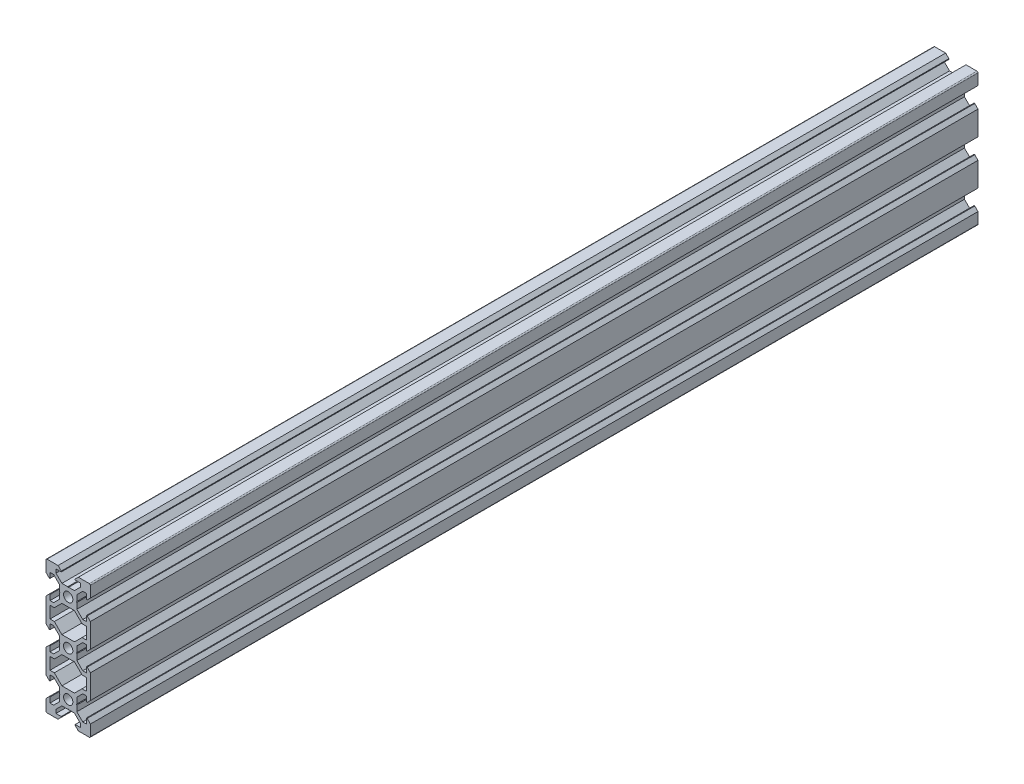
SolidWorks part; units mm, degrees
material "6061-T6 (SS)"
ref_plane "Front Plane" through (0, 0, 0) normal (0, 0, 1) x (1, 0, 0)
ref_plane "Top Plane" through (0, 0, 0) normal (0, 1, 0) x (1, 0, 0)
ref_plane "Right Plane" through (0, 0, 0) normal (1, 0, 0) x (0, 0, -1)
sketch "Sketch1" plane through (0, 0, 0) normal (0, 0, 1) x (1, 0, 0)
  line L0 (0, 0) -> (10, 0) construction
  line L1 (9.5, -30) -> (-9.5, -30)
  line L2 (10, -29.5) -> (10, 29.5)
  line L3 (9.5, 30) -> (-9.5, 30)
  line L4 (-10, -29.5) -> (-10, 29.5)
  line L5 (10, -30) -> (-10, 30) construction
  line L6 (10, 30) -> (-10, -30) construction
  circle A0 centre (0, 20) radius 2.1
  circle A1 centre (0, 0) radius 2.1
  circle A2 centre (0, -20) radius 2.1
  arc A3 (-9.5, -30) -> (-10, -29.5) centre (-9.5, -29.5) cw
  arc A4 (9.5, -30) -> (10, -29.5) centre (9.5, -29.5) ccw
  arc A5 (10, 29.5) -> (9.5, 30) centre (9.5, 29.5) ccw
  arc A6 (-9.5, 30) -> (-10, 29.5) centre (-9.5, 29.5) ccw
  point P0 (0, 0)
  line B0 (0, 20) -> (0, 30) construction
  line B1 (0, 23.69) -> (-0.21, 23.9)
  line B2 (-0.21, 23.9) -> (-2.8393, 23.9)
  line B3 (-2.8393, 23.9) -> (-5.5, 26.5607)
  line B4 (-5.5, 26.5607) -> (-5.5, 28.2)
  line B5 (-5.5, 28.2) -> (-3.125, 28.2)
  line B6 (-3.125, 28.2) -> (-3.125, 28.545)
  line B7 (-3.125, 28.545) -> (-4.58, 30)
  line B8 (-4.58, 30) -> (4.58, 30)
  line B9 (0, 20) -> (-5.9132, 25.9132) construction
  line B10 (3.125, 28.545) -> (4.58, 30)
  line B11 (3.125, 28.2) -> (3.125, 28.545)
  line B12 (5.5, 28.2) -> (3.125, 28.2)
  line B13 (5.5, 26.5607) -> (5.5, 28.2)
  line B14 (2.8393, 23.9) -> (5.5, 26.5607)
  line B15 (0.21, 23.9) -> (2.8393, 23.9)
  line B16 (0, 23.69) -> (0.21, 23.9)
  line B17 (0, 20) -> (-10, 20) construction
  line B18 (-3.69, 20) -> (-3.9, 19.79)
  line B19 (-3.9, 19.79) -> (-3.9, 17.1607)
  line B20 (-3.9, 17.1607) -> (-6.5607, 14.5)
  line B21 (-6.5607, 14.5) -> (-8.2, 14.5)
  line B22 (-8.2, 14.5) -> (-8.2, 16.875)
  line B23 (-8.2, 16.875) -> (-8.545, 16.875)
  line B24 (-8.545, 16.875) -> (-10, 15.42)
  line B25 (-10, 15.42) -> (-10, 24.58)
  line B26 (0, 20) -> (-5.9132, 14.0868) construction
  line B27 (-8.545, 23.125) -> (-10, 24.58)
  line B28 (-8.2, 23.125) -> (-8.545, 23.125)
  line B29 (-8.2, 25.5) -> (-8.2, 23.125)
  line B30 (-6.5607, 25.5) -> (-8.2, 25.5)
  line B31 (-3.9, 22.8393) -> (-6.5607, 25.5)
  line B32 (-3.9, 20.21) -> (-3.9, 22.8393)
  line B33 (-3.69, 20) -> (-3.9, 20.21)
  line B34 (0, 0) -> (-10, 0) construction
  line B35 (-3.69, 0) -> (-3.9, -0.21)
  line B36 (-3.9, -0.21) -> (-3.9, -2.8393)
  line B37 (-3.9, -2.8393) -> (-6.5607, -5.5)
  line B38 (-6.5607, -5.5) -> (-8.2, -5.5)
  line B39 (-8.2, -5.5) -> (-8.2, -3.125)
  line B40 (-8.2, -3.125) -> (-8.545, -3.125)
  line B41 (-8.545, -3.125) -> (-10, -4.58)
  line B42 (-10, -4.58) -> (-10, 4.58)
  line B43 (0, 0) -> (-5.9132, -5.9132) construction
  line B44 (-8.545, 3.125) -> (-10, 4.58)
  line B45 (-8.2, 3.125) -> (-8.545, 3.125)
  line B46 (-8.2, 5.5) -> (-8.2, 3.125)
  line B47 (-6.5607, 5.5) -> (-8.2, 5.5)
  line B48 (-3.9, 2.8393) -> (-6.5607, 5.5)
  line B49 (-3.9, 0.21) -> (-3.9, 2.8393)
  line B50 (-3.69, 0) -> (-3.9, 0.21)
  line B51 (0, -20) -> (-10, -20) construction
  line B52 (-3.69, -20) -> (-3.9, -20.21)
  line B53 (-3.9, -20.21) -> (-3.9, -22.8393)
  line B54 (-3.9, -22.8393) -> (-6.5607, -25.5)
  line B55 (-6.5607, -25.5) -> (-8.2, -25.5)
  line B56 (-8.2, -25.5) -> (-8.2, -23.125)
  line B57 (-8.2, -23.125) -> (-8.545, -23.125)
  line B58 (-8.545, -23.125) -> (-10, -24.58)
  line B59 (-10, -24.58) -> (-10, -15.42)
  line B60 (0, -20) -> (-5.9132, -25.9132) construction
  line B61 (-8.545, -16.875) -> (-10, -15.42)
  line B62 (-8.2, -16.875) -> (-8.545, -16.875)
  line B63 (-8.2, -14.5) -> (-8.2, -16.875)
  line B64 (-6.5607, -14.5) -> (-8.2, -14.5)
  line B65 (-3.9, -17.1607) -> (-6.5607, -14.5)
  line B66 (-3.9, -19.79) -> (-3.9, -17.1607)
  line B67 (-3.69, -20) -> (-3.9, -19.79)
  line B68 (0, -20) -> (0, -30) construction
  line B69 (0, -23.69) -> (0.21, -23.9)
  line B70 (0.21, -23.9) -> (2.8393, -23.9)
  line B71 (2.8393, -23.9) -> (5.5, -26.5607)
  line B72 (5.5, -26.5607) -> (5.5, -28.2)
  line B73 (5.5, -28.2) -> (3.125, -28.2)
  line B74 (3.125, -28.2) -> (3.125, -28.545)
  line B75 (3.125, -28.545) -> (4.58, -30)
  line B76 (4.58, -30) -> (-4.58, -30)
  line B77 (0, -20) -> (5.9132, -25.9132) construction
  line B78 (-3.125, -28.545) -> (-4.58, -30)
  line B79 (-3.125, -28.2) -> (-3.125, -28.545)
  line B80 (-5.5, -28.2) -> (-3.125, -28.2)
  line B81 (-5.5, -26.5607) -> (-5.5, -28.2)
  line B82 (-2.8393, -23.9) -> (-5.5, -26.5607)
  line B83 (-0.21, -23.9) -> (-2.8393, -23.9)
  line B84 (0, -23.69) -> (-0.21, -23.9)
  line B85 (0, -20) -> (10, -20) construction
  line B86 (3.69, -20) -> (3.9, -19.79)
  line B87 (3.9, -19.79) -> (3.9, -17.1607)
  line B88 (3.9, -17.1607) -> (6.5607, -14.5)
  line B89 (6.5607, -14.5) -> (8.2, -14.5)
  line B90 (8.2, -14.5) -> (8.2, -16.875)
  line B91 (8.2, -16.875) -> (8.545, -16.875)
  line B92 (8.545, -16.875) -> (10, -15.42)
  line B93 (10, -15.42) -> (10, -24.58)
  line B94 (0, -20) -> (5.9132, -14.0868) construction
  line B95 (8.545, -23.125) -> (10, -24.58)
  line B96 (8.2, -23.125) -> (8.545, -23.125)
  line B97 (8.2, -25.5) -> (8.2, -23.125)
  line B98 (6.5607, -25.5) -> (8.2, -25.5)
  line B99 (3.9, -22.8393) -> (6.5607, -25.5)
  line B100 (3.9, -20.21) -> (3.9, -22.8393)
  line B101 (3.69, -20) -> (3.9, -20.21)
  line B102 (0, 0) -> (10, 0) construction
  line B103 (3.69, 0) -> (3.9, 0.21)
  line B104 (3.9, 0.21) -> (3.9, 2.8393)
  line B105 (3.9, 2.8393) -> (6.5607, 5.5)
  line B106 (6.5607, 5.5) -> (8.2, 5.5)
  line B107 (8.2, 5.5) -> (8.2, 3.125)
  line B108 (8.2, 3.125) -> (8.545, 3.125)
  line B109 (8.545, 3.125) -> (10, 4.58)
  line B110 (10, 4.58) -> (10, -4.58)
  line B111 (0, 0) -> (5.9132, 5.9132) construction
  line B112 (8.545, -3.125) -> (10, -4.58)
  line B113 (8.2, -3.125) -> (8.545, -3.125)
  line B114 (8.2, -5.5) -> (8.2, -3.125)
  line B115 (6.5607, -5.5) -> (8.2, -5.5)
  line B116 (3.9, -2.8393) -> (6.5607, -5.5)
  line B117 (3.9, -0.21) -> (3.9, -2.8393)
  line B118 (3.69, 0) -> (3.9, -0.21)
  line B119 (0, 20) -> (10, 20) construction
  line B120 (3.69, 20) -> (3.9, 20.21)
  line B121 (3.9, 20.21) -> (3.9, 22.8393)
  line B122 (3.9, 22.8393) -> (6.5607, 25.5)
  line B123 (6.5607, 25.5) -> (8.2, 25.5)
  line B124 (8.2, 25.5) -> (8.2, 23.125)
  line B125 (8.2, 23.125) -> (8.545, 23.125)
  line B126 (8.545, 23.125) -> (10, 24.58)
  line B127 (10, 24.58) -> (10, 15.42)
  line B128 (0, 20) -> (5.9132, 25.9132) construction
  line B129 (8.545, 16.875) -> (10, 15.42)
  line B130 (8.2, 16.875) -> (8.545, 16.875)
  line B131 (8.2, 14.5) -> (8.2, 16.875)
  line B132 (6.5607, 14.5) -> (8.2, 14.5)
  line B133 (3.9, 17.1607) -> (6.5607, 14.5)
  line B134 (3.9, 19.79) -> (3.9, 17.1607)
  line B135 (3.69, 20) -> (3.9, 19.79)
  line B136 (-8.2, 7.3) -> (-8.2, 12.7)
  line B137 (-8.2, 12.7) -> (-6.2393, 12.7)
  line B138 (-6.2393, 12.7) -> (-2.8393, 16.1)
  line B139 (-2.8393, 16.1) -> (2.8393, 16.1)
  line B140 (0, 16.1) -> (0, 10) construction
  line B141 (0, 10) -> (-8.2, 10) construction
  line B142 (6.2393, 12.7) -> (2.8393, 16.1)
  line B143 (8.2, 12.7) -> (6.2393, 12.7)
  line B144 (8.2, 7.3) -> (8.2, 12.7)
  line B145 (8.2, 7.3) -> (6.2393, 7.3)
  line B146 (6.2393, 7.3) -> (2.8393, 3.9)
  line B147 (-2.8393, 3.9) -> (2.8393, 3.9)
  line B148 (-6.2393, 7.3) -> (-2.8393, 3.9)
  line B149 (-8.2, 7.3) -> (-6.2393, 7.3)
  line B150 (0, 16.1) -> (0, 20) construction
  line B151 (0, 20) -> (-5.0927, 14.9073) construction
  line B152 (-8.2, -12.7) -> (-8.2, -7.3)
  line B153 (-8.2, -7.3) -> (-6.2393, -7.3)
  line B154 (-6.2393, -7.3) -> (-2.8393, -3.9)
  line B155 (-2.8393, -3.9) -> (2.8393, -3.9)
  line B156 (0, -3.9) -> (0, -10) construction
  line B157 (0, -10) -> (-8.2, -10) construction
  line B158 (6.2393, -7.3) -> (2.8393, -3.9)
  line B159 (8.2, -7.3) -> (6.2393, -7.3)
  line B160 (8.2, -12.7) -> (8.2, -7.3)
  line B161 (8.2, -12.7) -> (6.2393, -12.7)
  line B162 (6.2393, -12.7) -> (2.8393, -16.1)
  line B163 (-2.8393, -16.1) -> (2.8393, -16.1)
  line B164 (-6.2393, -12.7) -> (-2.8393, -16.1)
  line B165 (-8.2, -12.7) -> (-6.2393, -12.7)
  line B166 (0, -3.9) -> (0, 0) construction
  line B167 (0, 0) -> (-5.0927, -5.0927) construction
  dimension "D3" = 4.2
  dimension "D5" = 0.5
  dimension "D1" = 20
  dimension "D2" = 60
  dimension "D4" = 40
sketch_block_instance "V Slot 1-4"
sketch_block "V Slot 1" parameters "D1"=10, "D2"=11, "D3"=4.3, "D4"=1.8, "D5"=0.21, "D6"=45, "D7"=9.16, "D8"=1.5, "D9"=6.25
sketch_block_instance "V Slot 1-5"
sketch_block_instance "V Slot 1-6"
sketch_block_instance "V Slot 1-7"
sketch_block_instance "V Slot 1-8"
sketch_block_instance "V Slot 1-9"
sketch_block_instance "V Slot 1-10"
sketch_block_instance "V Slot 1-11"
sketch_block_instance "Center Cutout 1-1"
sketch_block "Center Cutout 1" parameters "D1"=5.4, "D2"=12.2, "D3"=8.2, "D4"=45, "D5"=10, "D6"=1.5
sketch_block_instance "Center Cutout 1-2"
extrude "Boss-Extrude1" add sketch "Sketch1" along normal blind 400 contours B135 B120 B121 B122 B123 B124 B125 B126 L2 A5 L3 B10 B11 B12 B13 B14 B15 B16 B1 B2 B3 B4 B5 B6 B7 A6 L4 B27 B28 B29 B30 B31 B32 B33 B18 B19 B20 B21 B22 B23 B24 B44 B45 B46 B47 B48 B49 B50 B35 region at (7.04, -29.3675, 0)
